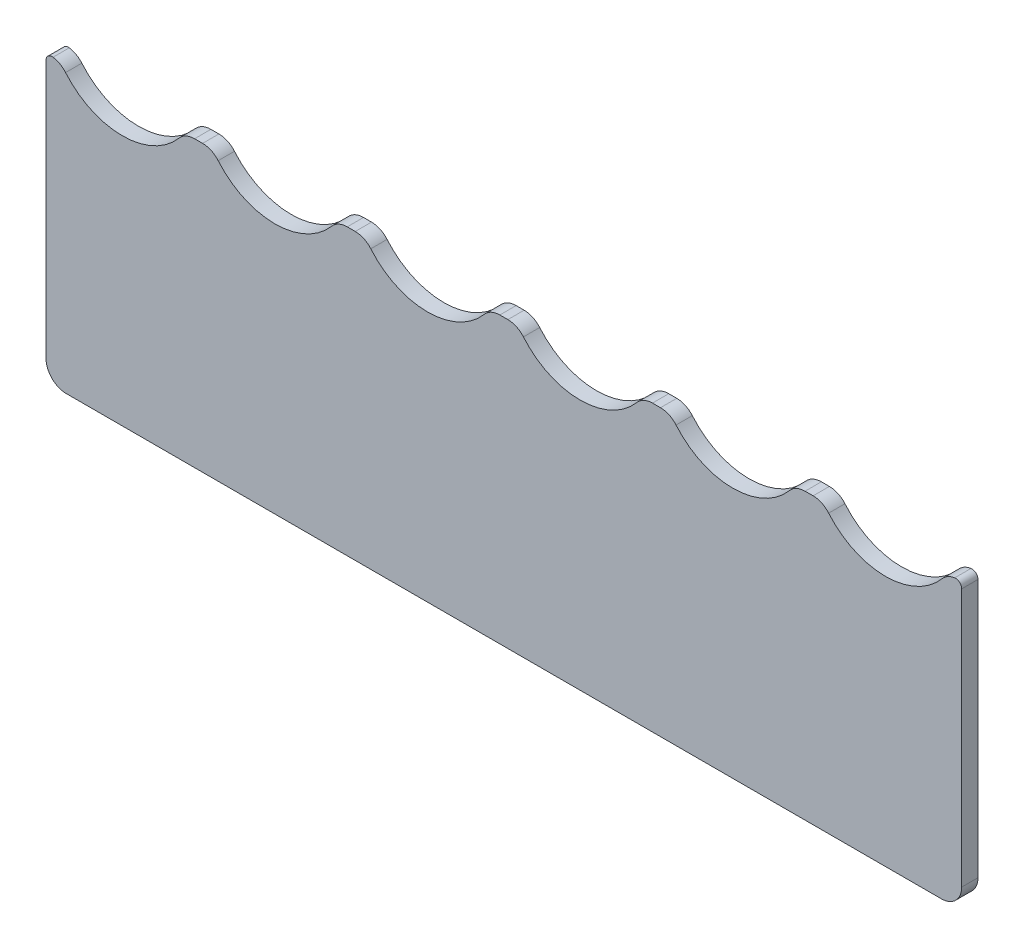
SolidWorks part; units mm, degrees
ref_plane "Plan de face" through (0, 0, 0) normal (0, 0, 1) x (1, 0, 0)
ref_plane "Plan de dessus" through (0, 0, 0) normal (0, 1, 0) x (1, 0, 0)
ref_plane "Plan de droite" through (0, 0, 0) normal (1, 0, 0) x (0, 0, -1)
sketch "Esquisse1" plane through (0, 0, 0) normal (0, 0, 1) x (1, 0, 0)
  line L0 (225, 0) -> (225, 140) construction
  line L1 (0, 0) -> (450, 0)
  line L2 (0, 0) -> (0, 140)
  line L3 (0, 140) -> (450, 140)
  line L4 (450, 0) -> (450, 140)
  dimension "D1" = 450
  dimension "D2" = 140
extrude "Boss.-Extru.1" add sketch "Esquisse1" along normal blind 8
sketch "Esquisse2" plane through (0, 0, 8) normal (0, 0, 1) x (1, 0, 0)
  line L0 (225, 0) -> (225, 140) construction
  line L1 (0, 0) -> (450, 0) construction
  line L2 (450, 140) -> (0, 140) construction
  line L3 (187.5, 160) -> (187.5, 87.5884) construction
  line L4 (187.5, 87.5884) -> (225, 87.5884) construction
  line L5 (37.5, 160) -> (112.5, 160) construction
  line L6 (112.5, 160) -> (187.5, 160) construction
  line L7 (337.5, 160) -> (262.5, 160) construction
  line L8 (412.5, 160) -> (337.5, 160) construction
  circle A0 centre (187.5, 160) radius 36.5
  circle A1 centre (112.5, 160) radius 36.5
  circle A2 centre (37.5, 160) radius 36.5
  circle A3 centre (412.5, 160) radius 36.5
  circle A4 centre (337.5, 160) radius 36.5
  circle A5 centre (262.5, 160) radius 36.5
  dimension "D1" = 73
  dimension "D2" = 75
  dimension "D3" = 75
  dimension "D5" = 20
  dimension "D4" = 37.5
extrude "Enlèv. mat.-Extru.1" cut sketch "Esquisse2" against normal through all both and the other way through all
fillet "Congé1" radius 10 14 edges at (6.9672, 140, 4) (443.0328, 140, 4) (381.9672, 140, 4) (368.0328, 140, 4) (306.9672, 140, 4) (293.0328, 140, 4) (231.9672, 140, 4) (218.0328, 140, 4) (156.9672, 140, 4) (143.0328, 140, 4) (81.9672, 140, 4) (68.0328, 140, 4) (450, 0, 4) (0, 0, 4)
fillet "Congé2" radius 3 2 edges at (450, 140, 4) (0, 140, 4)
